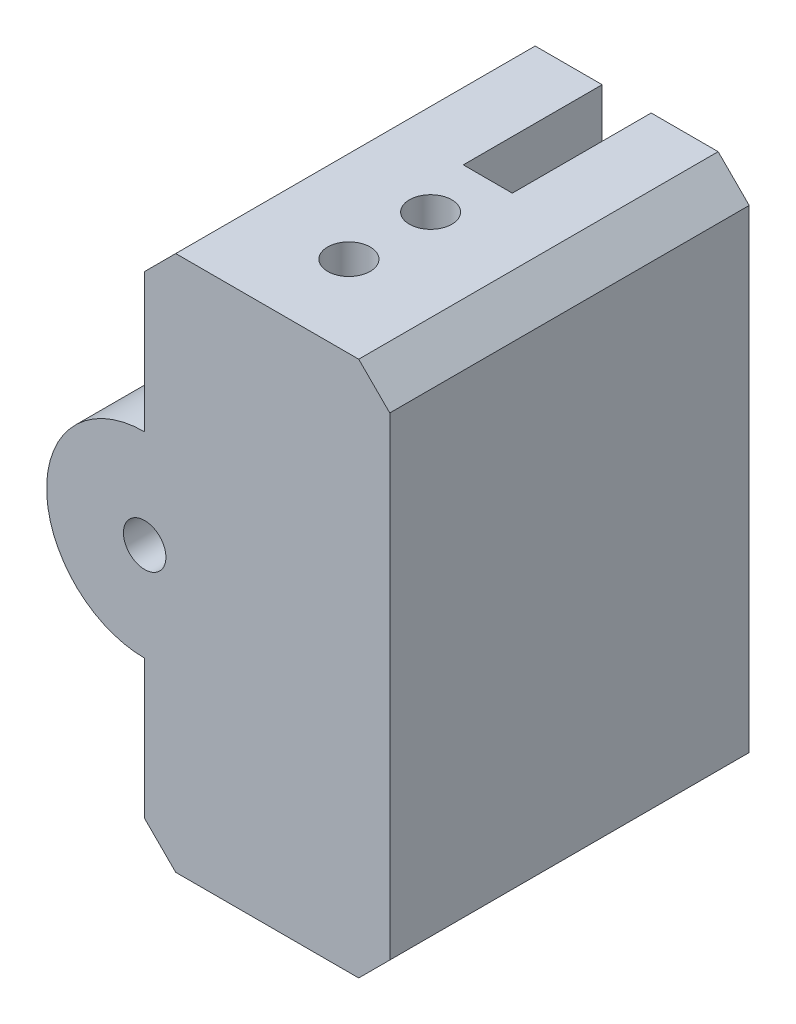
SolidWorks part; units mm, degrees
ref_plane "Front Plane" through (0, 0, 0) normal (0, 0, 1) x (1, 0, 0)
ref_plane "Top Plane" through (0, 0, 0) normal (0, 1, 0) x (1, 0, 0)
ref_plane "Right Plane" through (0, 0, 0) normal (1, 0, 0) x (0, 0, -1)
sketch "Sketch1" plane through (0, 0, 0) normal (0, 1, 0) x (1, 0, 0)
  line L0 (0, 0) -> (0, -17) construction
  line L1 (-7.5, 0) -> (7.5, 0)
  line L2 (-7.5, 0) -> (-7.5, -22)
  line L3 (-7.5, -22) -> (7.5, -22)
  line L4 (7.5, 0) -> (7.5, -22)
  line L5 (-1.5, -8.5) -> (1.5, -8.5)
  line L6 (-1.5, -8.5) -> (-1.5, 0)
  line L7 (-1.5, 0) -> (1.5, 0)
  line L8 (1.5, -8.5) -> (1.5, 0)
  circle A0 centre (0, -12) radius 1.3
  circle A1 centre (0, -17) radius 1.3
  point P5 (0, 0)
  point P12 (0, 0)
  dimension "D6" = 2.6
  dimension "D7" = 5
  dimension "D1" = 8.5
  dimension "D2" = 3
  dimension "D3" = 22
  dimension "D4" = 6
  dimension "D5" = 10
extrude "Boss-Extrude1" add sketch "Sketch1" along normal blind 32.8 contours L8 L5 A0 A1 L6 L1 L2 L3 L4 region at (-4.5, 0, 0.2663)
chamfer "Chamfer1" distance 1.9 angle 45 2 edges at (7.5, 32.8, 11) (7.5, 0, 11)
chamfer "Chamfer2" distance 1.9 angle 45 2 edges at (-7.5, 0, 11) (-7.5, 32.8, 11)
sketch "Sketch2" plane through (0, 0, 0) normal (0, 0, -1) x (-1, 0, 0)
  line L0 (7.5, 30.9) -> (7.5, 1.9) construction
  line L1 (1.5, 32.8) -> (1.5, 0) construction
  circle A0 centre (7.5, 16.4) radius 6
extrude "Boss-Extrude2" add sketch "Sketch2" against normal blind 22
sketch "Sketch3" plane through (0, 0, 0) normal (0, 0, -1) x (-1, 0, 0)
  circle A0 centre (7.5, 16.4) radius 1.3
  dimension "D1" = 2.6
extrude "Cut-Extrude1" cut sketch "Sketch3" against normal through all both and the other way through all
